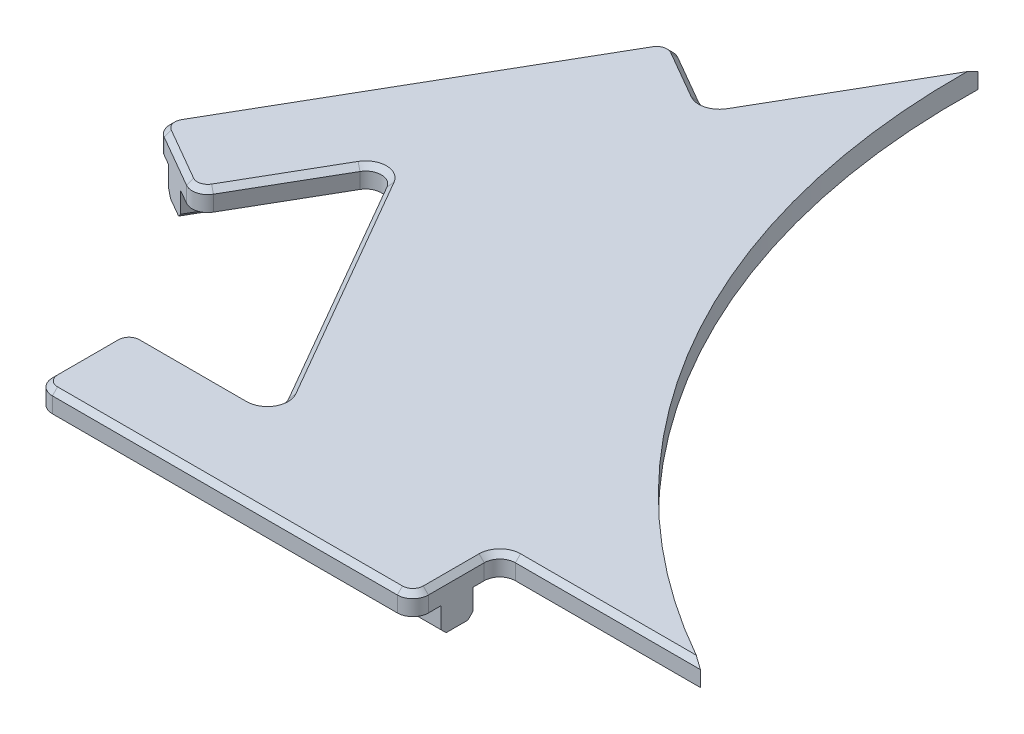
SolidWorks part; units mm, degrees
ref_plane "Front Plane" through (0, 0, 0) normal (0, 0, 1) x (1, 0, 0)
ref_plane "Top Plane" through (0, 0, 0) normal (0, 1, 0) x (1, 0, 0)
ref_plane "Right Plane" through (0, 0, 0) normal (1, 0, 0) x (0, 0, -1)
sketch "Sketch1" plane through (0, 0, 0) normal (0, 1, 0) x (1, 0, 0)
  line L9 (0, 0) -> (48, 0) construction
  line L10 (48, 0) -> (404, 0) construction
  line L11 (404, 0) -> (452, 0) construction
  line L12 (452, 0) -> (428, 41.5692) construction
  line L13 (428, 41.5692) -> (250, 349.8743) construction
  line L14 (250, 349.8743) -> (226, 391.4435) construction
  line L15 (226, 391.4435) -> (202, 349.8743) construction
  line L16 (202, 349.8743) -> (24, 41.5692) construction
  line L17 (24, 41.5692) -> (0, 0) construction
  line L18 (48, 0) -> (24, 41.5692) construction
  line L19 (202, 349.8743) -> (250, 349.8743) construction
  line L20 (428, 41.5692) -> (404, 0) construction
  line L22 (15.3397, 46.5692) -> (193.3397, 354.8743) construction
  line L28 (404, -10) -> (48, -10) construction
  line L30 (48, -10) -> (48, 10) construction
  line L31 (404, -10) -> (404, 10) construction
  line L32 (15.3397, 46.5692) -> (32.6603, 36.5692) construction
  line L33 (193.3397, 354.8743) -> (210.6603, 344.8743) construction
  line L34 (404, 10) -> (48, 10) construction
  line L35 (32.6603, 36.5692) -> (210.6603, 344.8743) construction
  line L45 (76, 10) -> (46.6603, 60.8179)
  line L51 (0, 0) -> (339, 195.7217) construction
  line L52 (76, 10) -> (76, 8.5)
  line L53 (76, 8.5) -> (48, 8.5)
  line L54 (48, 8.5) -> (48, -9.25)
  line L55 (48, -9.25) -> (120.45, -9.25)
  line L56 (120.45, -9.25) -> (120.45, 7.5)
  line L57 (120.45, 7.5) -> (159.0998, 7.5)
  line L58 (159.0998, 7.5) -> (86.0451, 134.0345)
  line L59 (52.2143, 108.9378) -> (66.7202, 100.5628)
  line L60 (66.7202, 100.5628) -> (86.0451, 134.0345)
  line L61 (46.6603, 60.8179) -> (45.3612, 61.5679)
  line L62 (45.3612, 61.5679) -> (31.3612, 37.3192)
  line L63 (31.3612, 37.3192) -> (15.9893, 46.1942)
  line L64 (15.9893, 46.1942) -> (52.2143, 108.9378)
  line L65 (226, 391.4435) -> (226, 0) construction
  line L66 (452, 0) -> (113, 195.7217) construction
  arc A0 (48, -10) -> (15.3397, 46.5692) centre (48, 27.7128) cw construction
  circle A3 centre (226, 130.4812) radius 140 construction
  point P32 (122.5725, 70.7672)
  point P33 (61.3301, 35.409)
  point P40 (0, 0)
  dimension "D7" = 72.45
  dimension "D10" = 280
  dimension "D1" = 356
  dimension "D2" = 48
  dimension "D3" = 10
  dimension "D4" = 28
  dimension "D5" = 1.5
  dimension "D6" = 1.5
  dimension "D8" = 17.5
extrude "Boss-Extrude1" add sketch "Sketch1" along normal blind 4
fillet "Fillet1" radius 3 8 edges at (66.7202, 2, -100.5628) (120.45, 2, -7.5) (52.2143, 2, -108.9378) (15.9893, 2, -46.1942) (48, 2, -8.5) (48, 2, 9.25) (120.45, 2, 9.25) (31.3612, 2, -37.3192)
sketch "Sketch2" plane through (0, 4, 0) normal (0, 1, 0) x (1, 0, 0)
  line L0 (46.6603, 60.8179) -> (45.7942, 62.3179)
  line L1 (45.7942, 62.3179) -> (45.3612, 61.5679)
  line L2 (45.3612, 61.5679) -> (46.6603, 60.8179)
  line L3 (76, 8.5) -> (76.866, 8.5)
  line L4 (76.866, 8.5) -> (76, 10)
  line L5 (76, 10) -> (76, 8.5)
  line L6 (76, 8.5) -> (51, 8.5) construction
  line L7 (46.6603, 60.8179) -> (76, 10) construction
  line L8 (32.8612, 39.9173) -> (45.3612, 61.5679) construction
extrude "Cut-Extrude1" cut sketch "Sketch2" against normal through all
fillet "Fillet4" radius 3 2 edges at (76.866, 2, -8.5) (45.7942, 2, -62.3179)
chamfer "Chamfer1" distance 1 angle 45 21 edges at (31.0396, 4, -38.5195) (23.6752, 4, -41.7567) (17.1896, 4, -46.5158) (34.1018, 4, -77.566) (52.5359, 4, -107.7375) (59.4672, 4, -104.7503) (66.3986, 4, -101.7631) (77.1326, 4, -118.5977) (141.2749, 4, -7.5) (121.3287, 4, -6.6213) (120.45, 4, 0.875) (119.5713, 4, 8.3713) (84.225, 4, 9.25) (48.8787, 4, 8.3713) (48, 4, 0.375) (48.8787, 4, -7.6213) (61.3349, 4, -8.5) (74.2679, 4, -10) (61.3301, 4, -35.409) (45.7942, 4, -59.3179) (38.0287, 4, -48.8676)
sketch "Sketch3" plane through (0, 4, 0) normal (0, 1, 0) x (1, 0, 0)
  circle A0 centre (226, 130.4812) radius 140
  circle A1 centre (226, 130.4812) radius 140 construction
extrude "Cut-Extrude2" cut sketch "Sketch3" against normal through all
sketch "Sketch4" plane through (0, 0, 0) normal (0, -1, 0) x (1, 0, 0)
  line L0 (48, 0.75) -> (120.45, 0.75) construction
  line L1 (48, -5.5) -> (48, 6.25) construction
  line L2 (120.45, 6.25) -> (120.45, -4.5) construction
  line L3 (23.3505, -41.9442) -> (59.5755, -104.6878) construction
  line L4 (18.5873, -44.6942) -> (28.7631, -38.8192) construction
  line L5 (64.1221, -102.0628) -> (54.8123, -107.4378) construction
  line L6 (51, 9.25) -> (117.45, 9.25) construction
  line L7 (50.7143, -106.3397) -> (17.4893, -48.7923) construction
  line L8 (20.6658, -43.4942) -> (56.8908, -106.2378)
  line L9 (56.8908, -106.2378) -> (62.2602, -103.1378)
  line L10 (62.2602, -103.1378) -> (26.0352, -40.3942)
  line L12 (48, 0.75) -> (48, 3.85)
  line L13 (23.3505, -41.9442) -> (20.6658, -43.4942)
  line L14 (23.3505, -41.9442) -> (26.0352, -40.3942)
  line L15 (48, 3.85) -> (120.45, 3.85)
  line L16 (120.45, 3.85) -> (120.45, -2.35)
  line L17 (120.45, -2.35) -> (48, -2.35)
  line L18 (48, -2.35) -> (48, 0.75)
  point P24 (0, 0)
  point P25 (0, 0)
  dimension "D1" = 6.2
  dimension "D2" = 8.5
  dimension "D3" = 8.5
extrude "Boss-Extrude2" add sketch "Sketch4" along normal blind 5
chamfer "Chamfer2" distance 1 angle 45 4 edges at (38.7783, -5, -74.866) (44.1477, -5, -71.766) (84.225, -5, 3.85) (84.225, -5, -2.35)
